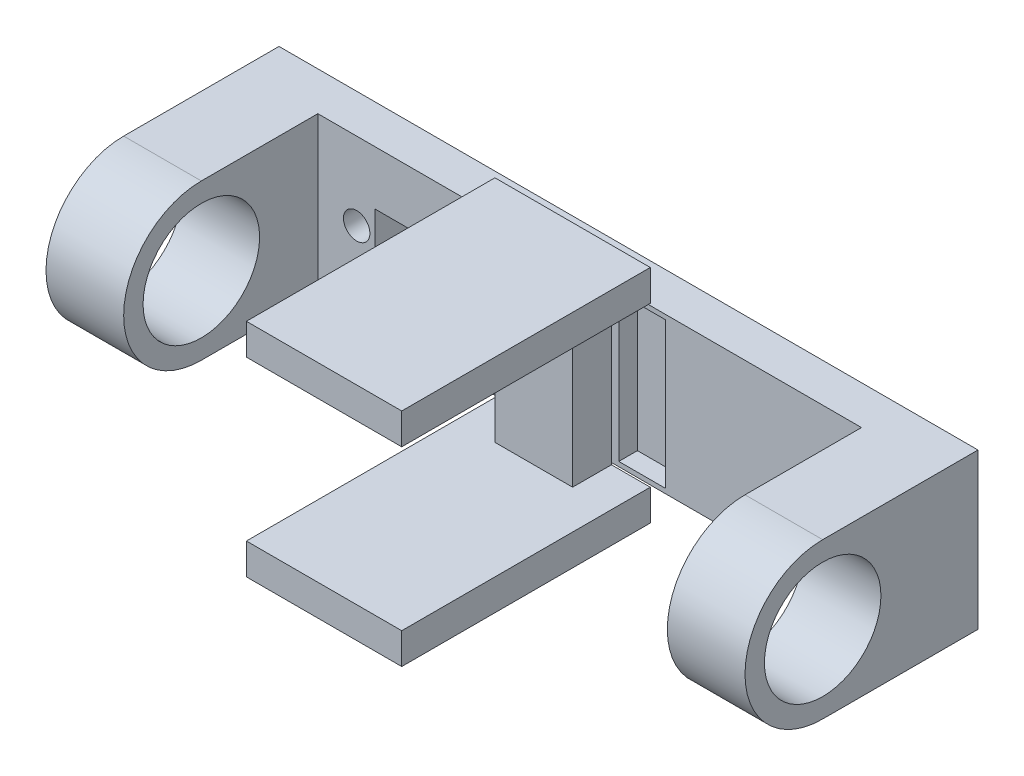
SolidWorks part; units mm, degrees
ref_plane "Plan de face" through (0, 0, 0) normal (0, 0, 1) x (1, 0, 0)
ref_plane "Plan de dessus" through (0, 0, 0) normal (0, 1, 0) x (1, 0, 0)
ref_plane "Plan de droite" through (0, 0, 0) normal (1, 0, 0) x (0, 0, -1)
sketch "Esquisse1" plane through (0, 0, 0) normal (0, 0, 1) x (1, 0, 0)
  line L1 (0, 0) -> (90, 0)
  line L2 (0, 0) -> (0, 20)
  line L3 (0, 20) -> (90, 20)
  line L4 (90, 0) -> (90, 20)
  dimension "D1" = 90
  dimension "D2" = 20
extrude "Boss.-Extru.1" add sketch "Esquisse1" along normal blind 5
sketch "Esquisse2" plane through (0, 0, 5) normal (0, 0, 1) x (1, 0, 0)
  line L0 (90, 20) -> (0, 20) construction
  line L1 (0, 0) -> (10, 0)
  line L2 (0, 0) -> (0, 20)
  line L3 (0, 20) -> (10, 20)
  line L4 (10, 0) -> (10, 20)
  dimension "D1" = 10
extrude "Boss.-Extru.2" add sketch "Esquisse2" along normal blind 30
sketch "Esquisse3" plane through (0, 0, 0) normal (-1, 0, 0) x (0, 0, 1)
  line L0 (0, 20) -> (0, 0) construction
  line L1 (35, 20) -> (0, 20) construction
  line L2 (35, 20) -> (35, 0) construction
  line L3 (35, 0) -> (0, 0) construction
  line L4 (35, 20) -> (20, 20)
  line L5 (35, 20) -> (35, 0)
  line L6 (35, 0) -> (20, 0)
  circle A0 centre (20, 10) radius 7.5
  arc A1 (20, 0) -> (20, 20) centre (20, 10) ccw
  dimension "D2" = 15
  dimension "D4" = 20
  dimension "D1" = 20
  dimension "D3" = 10
extrude "Enlèv. mat.-Extru.1" cut sketch "Esquisse3" against normal up to surface (10 mm away) up to face at (10, 10, 20)
ref_plane "Plan1" through (45, 0, 0) normal (1, 0, 0) x (0, 0, -1)
mirror "Symétrie1" about plane through (45, 0, 0) normal (1, 0, 0) of "Enlèv. mat.-Extru.1", "Boss.-Extru.2"
sketch "Esquisse5" plane through (0, 0, 5) normal (0, 0, 1) x (1, 0, 0)
  line L0 (80, 20) -> (10, 20) construction
  line L1 (48.75, 19.4) -> (54.75, 19.4)
  line L2 (48.75, 19.4) -> (48.75, 0.6)
  line L3 (48.75, 0.6) -> (54.75, 0.6)
  line L4 (54.75, 19.4) -> (54.75, 0.6)
  line L10 (45, -11) -> (45, 11) construction
  point P7 (51.75, 19.4)
  dimension "D1" = 18.8
  dimension "D2" = 6
  dimension "D3" = 0.6
  dimension "D4" = 6.75
extrude "Enlèv. mat.-Extru.2" cut sketch "Esquisse5" against normal offset from surface (2.4 mm away) 2.6 up to face at (45, 10, 0)
sketch "Esquisse6" plane through (0, 0, 5) normal (0, 0, 1) x (1, 0, 0)
  line L0 (80, 20) -> (10, 20) construction
  line L1 (10, 0) -> (10, 20) construction
  line L2 (80, 20) -> (80, 0) construction
  circle A0 centre (25, 10) radius 1.5 construction
  circle A1 centre (68, 10) radius 1.5
  dimension "D1" = 3
  dimension "D4" = 3
  dimension "D2" = 10
  dimension "D3" = 15
  dimension "D5" = 10
  dimension "D6" = 12
extrude "Enlèv. mat.-Extru.3" [suppressed] cut sketch "Esquisse6" against normal up to surface (5 mm away) up to face at (45, 10, 0)
sketch "Esquisse10" plane through (0, 0, 5) normal (0, 0, 1) x (1, 0, 0)
  line L0 (48.75, 19.4) -> (48.75, 0.6) construction
  line L1 (17.35, 13.05) -> (32.35, 13.05)
  line L2 (17.35, 13.05) -> (17.35, 6.95)
  line L3 (17.35, 6.95) -> (32.35, 6.95)
  line L4 (32.35, 13.05) -> (32.35, 6.95)
  line L5 (80, 20) -> (10, 20) construction
  point P6 (32.35, 10)
  dimension "D1" = 16.4
  dimension "D2" = 15
  dimension "D3" = 6.1
  dimension "D4" = 10
extrude "Enlèv. mat.-Extru.4" cut sketch "Esquisse10" against normal up to surface (5 mm away) up to face at (45, 10, 0)
sketch "Esquisse11" plane through (0, 0, 5) normal (0, 0, 1) x (1, 0, 0)
  line L0 (0, 10) -> (91.8744, 10) construction
  line L2 (45, -11) -> (45, 11) construction
  line L4 (0, 20) -> (0, 0)
  line L5 (90, 20) -> (0, 20)
  line L6 (90, 0) -> (90, 20)
  line L7 (0, 0) -> (90, 0)
  line L8 (0, 20) -> (0, 0) construction
  line L9 (90, 20) -> (0, 20) construction
  line L10 (90, 0) -> (90, 20) construction
  line L11 (0, 0) -> (90, 0) construction
  circle A0 centre (15, 10) radius 1
  circle A1 centre (75, 10) radius 1
  dimension "D2" = 2
  dimension "D3" = 2
  dimension "D4" = 30
  dimension "D5" = 30
  dimension "D1" = 0
extrude "Enlèv. mat.-Extru.5" cut sketch "Esquisse11" against normal blind 10
hole_wizard "Dégagement M31" positions "Esquisse12" profile "Esquisse13" hole size "M3" standard "ISO" end condition through all
sketch "Esquisse12" plane through (0, 0, 5) normal (0, 0, 1) x (1, 0, 0)
  point P0 (15, 10)
  point P3 (75, 10)
sketch "Esquisse13" plane through (15, 10, 5) normal (1, 0, 0) x (0, -1, 0)
  line L0 (0, 0) -> (0, 5)
  line L1 (0, 5) -> (1.7, 5)
  line L2 (1.7, 5) -> (1.7, 0)
  line L5 (1.7, 0) -> (0, 0)
  line L11 (0, -6.35) -> (0, 107.95) construction
  dimension "Diamètre du perçage jusqu'au prochain" = 3.4
  dimension "Profondeur du perçage jusqu'au prochain" = 5
sketch "Esquisse14" plane through (0, 0, 5) normal (0, 0, 1) x (1, 0, 0)
  line L0 (10, 0) -> (80, 0) construction
  line L1 (37.8031, 24.2512) -> (47.8031, 24.2512)
  line L2 (37.8031, 24.2512) -> (37.8031, -4.2488)
  line L3 (37.8031, -4.2488) -> (47.8031, -4.2488)
  line L4 (47.8031, 24.2512) -> (47.8031, -4.2488)
  line L6 (45, -11) -> (45, 11) construction
  point P4 (37.8031, 10.0012)
  point P7 (42.8031, 24.2512)
  dimension "D1" = 28.5
  dimension "D2" = 10.0012
  dimension "D3" = 10
  dimension "D4" = 2.1969
extrude "Boss.-Extru.3" add sketch "Esquisse14" along normal blind 5
sketch "Esquisse16" plane through (0, 0, 10) normal (0, 0, 1) x (1, 0, 0)
  line L1 (32.8031, 24.2512) -> (52.8031, 24.2512)
  line L2 (32.8031, 24.2512) -> (32.8031, 20.2512)
  line L3 (32.8031, 20.2512) -> (52.8031, 20.2512)
  line L4 (52.8031, 24.2512) -> (52.8031, 20.2512)
  line L5 (37.8031, -4.2488) -> (47.8031, -4.2488) construction
  line L10 (32.8031, -0.2488) -> (52.8031, -0.2488)
  line L11 (47.8031, 24.2512) -> (37.8031, 24.2512) construction
  line L12 (32.8031, -0.2488) -> (32.8031, -4.2488)
  line L13 (32.8031, -4.2488) -> (52.8031, -4.2488)
  line L14 (52.8031, -0.2488) -> (52.8031, -4.2488)
  point P13 (42.8031, 24.2512)
  point P14 (42.8031, 24.2512)
  point P15 (42.8031, -4.2488)
  point P16 (42.8031, -4.2488)
  dimension "D1" = 4
  dimension "D2" = 4
  dimension "D3" = 20
  dimension "D4" = 20
extrude "Boss.-Extru.4" add sketch "Esquisse16" along normal blind 32 from surface starting at face at (42.8031, -2.1244, 5)
equation "\"D3@Esquisse5\"=(20-\"D1@Esquisse5\")/2"
